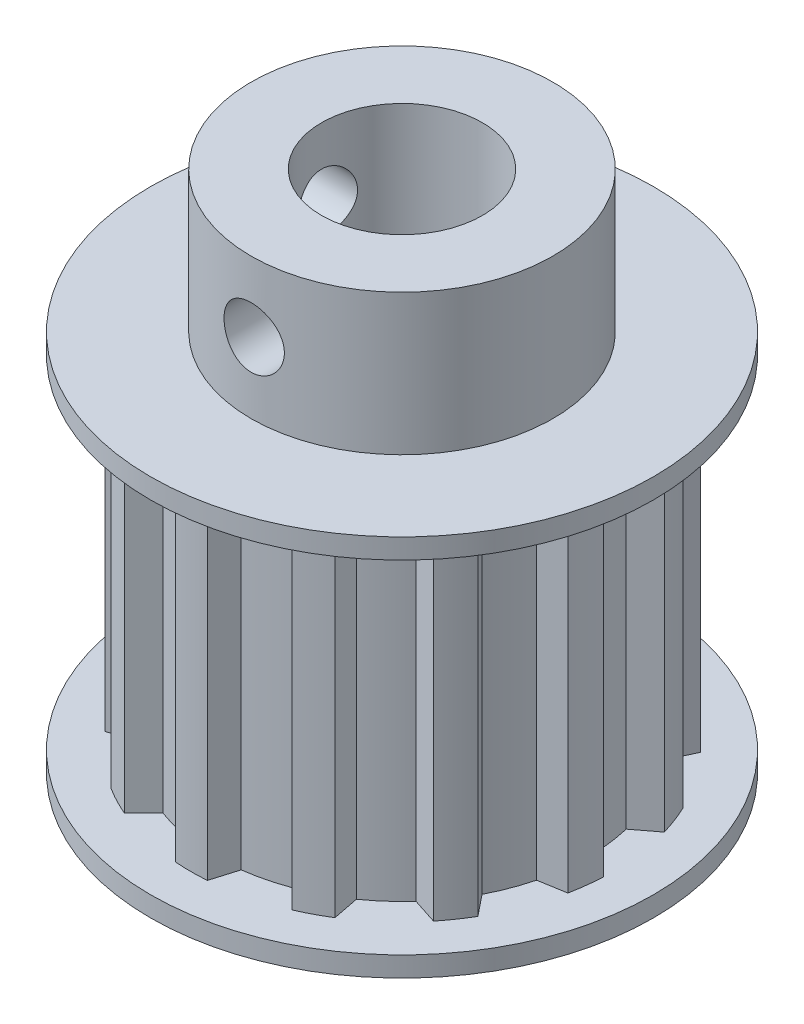
SolidWorks part; units mm, degrees
ref_plane "Alzado" through (0, 0, 0) normal (0, 0, 1) x (1, 0, 0)
ref_plane "Planta" through (0, 0, 0) normal (0, 1, 0) x (1, 0, 0)
ref_plane "Vista lateral" through (0, 0, 0) normal (1, 0, 0) x (0, 0, -1)
sketch "Croquis1" plane through (0, 0, 0) normal (0, 1, 0) x (1, 0, 0)
  circle A0 centre (0, 0) radius 12.5
  dimension "D1" = 25
extrude "Saliente-Extruir1" add sketch "Croquis1" along normal blind 1
sketch "Croquis3" plane through (0, 1, 0) normal (0, 1, 0) x (1, 0, 0)
  circle A0 centre (0, 0) radius 10.5
  dimension "D1" = 21
extrude "Saliente-Extruir2" add sketch "Croquis3" along normal blind 17
sketch "Croquis5" plane through (0, 18, 0) normal (0, 1, 0) x (1, 0, 0)
  line L0 (0, 10.55) -> (0, -10.55) construction
  line L1 (0, 9.25) -> (-1.05, 9.1902)
  line L2 (0, 9.25) -> (1.05, 9.1902)
  line L3 (1.05, 9.1902) -> (1.5451, 9.12) construction
  line L4 (-1.05, 9.1902) -> (-1.5451, 9.12) construction
  line L5 (-1.5451, 9.12) -> (-1.7622, 10.4018) construction
  line L6 (1.5451, 9.12) -> (1.7622, 10.4018) construction
  line L7 (-1.05, 9.1902) -> (-1.7622, 10.4018)
  line L8 (1.05, 9.1902) -> (1.7622, 10.4018)
  circle A0 centre (0, 0) radius 10.55
  circle A1 centre (0, 0) radius 9.25
  circle A3 centre (0, 0) radius 10.5
  circle A4 centre (0, 0) radius 10.5
  circle M2 centre (0, 0) radius 10.5
  dimension "D1" = 21.1
  dimension "D2" = 1.3
  dimension "D3" = 1.05
  dimension "D4" = 0.5
  dimension "D5" = 0.5
  dimension "D6" = 0
extrude "Cortar-Extruir1" cut sketch "Croquis5" against normal up to surface (17 mm away) contours A1 L8 L7 M2 region at (0, 18, -9.8919) up to face at (0, 1, 12.5)
pattern_circular "MatrizC1" count 13 over 360 about axis through (0, 18, 0) along (0, 1, 0) of "Cortar-Extruir1"
sketch "Croquis6" plane through (0, 18, 0) normal (0, 1, 0) x (1, 0, 0)
  circle A0 centre (0, 0) radius 12.5
  dimension "D1" = 25
extrude "Saliente-Extruir3" add sketch "Croquis6" along normal blind 1
sketch "Croquis7" plane through (0, 19, 0) normal (0, 1, 0) x (1, 0, 0)
  circle A0 centre (0, 0) radius 7.5
  dimension "D1" = 15
extrude "Saliente-Extruir4" add sketch "Croquis7" along normal blind 7
sketch "Croquis8" plane through (0, 26, 0) normal (0, 1, 0) x (1, 0, 0)
  circle A0 centre (0, 0) radius 7.5 construction
  circle A1 centre (0, 0) radius 7.5 construction
  point P0 (-7.5, 0)
  point P1 (0, -7.5)
ref_plane "Plano1" through (0, 26, 7.5) normal (0, 0, 1) x (1, 0, 0)
sketch "Croquis9" plane through (0, 26, 7.5) normal (0, 0, 1) x (1, 0, 0)
  line L0 (0, 0) -> (0, -7) construction
  line L1 (12.5, -7) -> (-12.5, -7) construction
  circle A0 centre (0, -3.5) radius 1.5
  dimension "D1" = 3
ref_plane "Plano2" through (-7.5, 26, 0) normal (-1, 0, 0) x (0, 0, 1)
sketch "Croquis10" plane through (-7.5, 26, 0) normal (-1, 0, 0) x (0, 0, 1)
  line L0 (0, 0) -> (0, -7) construction
  line L1 (12.5, -7) -> (-12.5, -7) construction
  circle A0 centre (0, -3.5) radius 1.5
  dimension "D1" = 3
sketch "Croquis11" plane through (0, 26, 0) normal (0, 1, 0) x (1, 0, 0)
  circle A0 centre (0, 0) radius 4
  dimension "D1" = 8
extrude "Cortar-Extruir2" cut sketch "Croquis11" against normal blind 37
extrude "Cortar-Extruir3" cut sketch "Croquis9" against normal blind 7
extrude "Cortar-Extruir4" cut sketch "Croquis10" against normal blind 7
